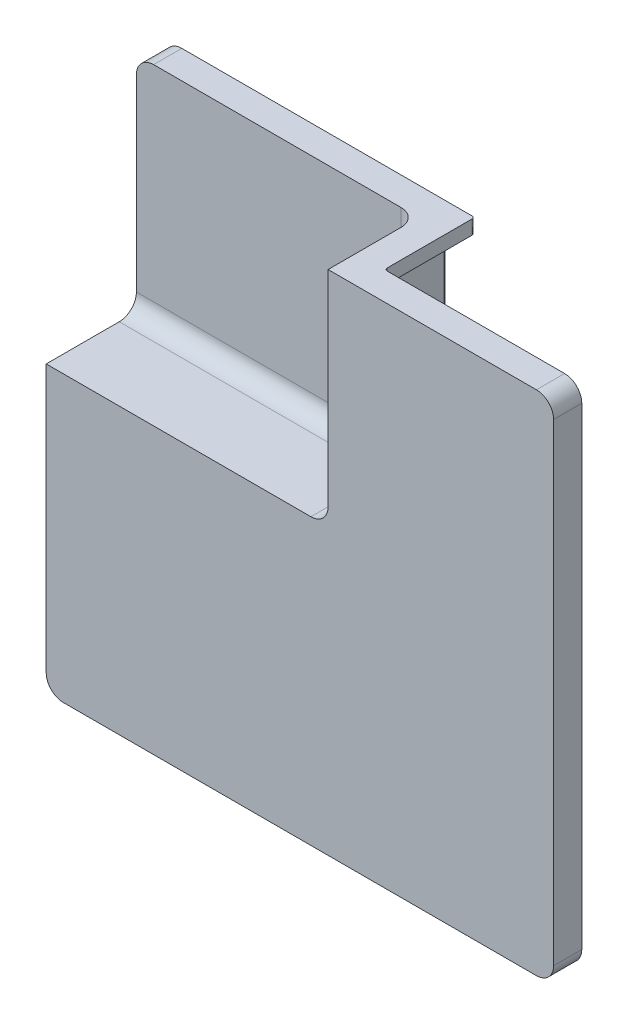
SolidWorks part; units mm, degrees
ref_plane "Front Plane" through (0, 0, 0) normal (0, 0, 1) x (1, 0, 0)
ref_plane "Top Plane" through (0, 0, 0) normal (0, 1, 0) x (1, 0, 0)
ref_plane "Right Plane" through (0, 0, 0) normal (1, 0, 0) x (0, 0, -1)
sketch "Sketch1" plane through (0, 0, 0) normal (0, 0, 1) x (1, 0, 0)
  line L1 (-57.2063, 108.3793) -> (110.5937, 108.3793)
  line L2 (-63.3063, 102.2793) -> (-63.3063, -65.5207)
  line L3 (-57.2063, -71.6207) -> (110.5937, -71.6207)
  line L4 (116.6937, 102.2793) -> (116.6937, -65.5207)
  arc A0 (-57.2063, 108.3793) -> (-63.3063, 102.2793) centre (-57.2063, 102.2793) ccw
  arc A1 (116.6937, 102.2793) -> (110.5937, 108.3793) centre (110.5937, 102.2793) ccw
  arc A2 (110.5937, -71.6207) -> (116.6937, -65.5207) centre (110.5937, -65.5207) ccw
  arc A3 (-63.3063, -65.5207) -> (-57.2063, -71.6207) centre (-57.2063, -65.5207) ccw
  dimension "D3" = 12.2
  dimension "D1" = 180
  dimension "D4" = 2
extrude "Boss-Extrude1" add sketch "Sketch1" along normal blind 5 contours A0 L2 L3 L4 L1 region at (26.6937, 18.3793, 0)
sketch "Sketch3" plane through (0, 0, 5) normal (0, 0, 1) x (1, 0, 0)
  line L0 (-63.3067, 18.3794) -> (116.6933, 18.3794) construction
  line L1 (26.6933, 108.3794) -> (26.6933, -71.6206) construction
  line L2 (-52.2067, -66.6206) -> (105.5933, -66.6206)
  line L3 (-58.3067, -60.5206) -> (-58.3067, 97.2794)
  line L4 (-52.2067, 103.3794) -> (105.5933, 103.3794)
  line L5 (111.6933, -60.5206) -> (111.6933, 97.2794)
  line L6 (-58.3067, -66.6206) -> (111.6933, 103.3794) construction
  line L7 (-58.3067, 103.3794) -> (111.6933, -66.6206) construction
  circle A0 centre (-52.2067, 97.2794) radius 6.1
  arc A1 (111.6933, 97.2794) -> (105.5933, 103.3794) centre (105.5933, 97.2794) ccw
  arc A2 (105.5933, -66.6206) -> (111.6933, -60.5206) centre (105.5933, -60.5206) ccw
  arc A3 (-58.3067, -60.5206) -> (-52.2067, -66.6206) centre (-52.2067, -60.5206) ccw
  point P4 (26.6933, 18.3794)
  line M1 (-63.3063, 102.2793) -> (-63.3063, -65.5207)
  arc M2 (-63.3063, -65.5207) -> (-57.2063, -71.6207) centre (-57.2063, -65.5207) ccw
  line M3 (-57.2063, -71.6207) -> (110.5937, -71.6207)
  arc M4 (110.5937, -71.6207) -> (116.6937, -65.5207) centre (110.5937, -65.5207) ccw
  line M5 (116.6937, -65.5207) -> (116.6937, 102.2793)
  arc M6 (116.6937, 102.2793) -> (110.5937, 108.3793) centre (110.5937, 102.2793) ccw
  line M7 (110.5937, 108.3793) -> (-57.2063, 108.3793)
  arc M8 (-57.2063, 108.3793) -> (-63.3063, 102.2793) centre (-57.2063, 102.2793) ccw
  dimension "D1" = 12.2
extrude "Boss-Extrude2" add sketch "Sketch3" against normal blind 10 contours A3 L3 A0 L4 A1 L5 A2 L2 M8 M1 M2 M3 M4 M5 M6 M7 region at (-59.7197, 104.7926, 5)
sketch "Sketch4" plane through (0, 0, 5) normal (0, 0, 1) x (1, 0, 0)
  line L0 (-63.3063, 102.2793) -> (-63.3063, -65.5207) construction
  line L1 (-63.3063, 29.3793) -> (36.6937, 29.3793)
  line L2 (-63.3063, 29.3793) -> (-63.3063, 108.3793)
  line L3 (-63.3063, 108.3793) -> (36.6937, 108.3793)
  line L4 (36.6937, 29.3793) -> (36.6937, 108.3793)
  line L5 (110.5937, 108.3793) -> (-57.2063, 108.3793) construction
  dimension "D1" = 100
  dimension "D2" = 79
extrude "Cut-Extrude1" cut sketch "Sketch4" against normal mid plane 60
sketch "Sketch5" plane through (0, 0, 5) normal (0, 0, 1) x (1, 0, 0)
  line L0 (36.6937, 29.3793) -> (36.6937, 108.3793) construction
  line L1 (36.6937, 108.3793) -> (41.6937, 108.3793)
  line L2 (36.6937, 108.3793) -> (36.6937, 35.4793)
  line L4 (41.6937, 108.3793) -> (41.6937, 30.4793)
  line L5 (30.5937, 29.3793) -> (-63.3063, 29.3793)
  line L8 (-63.3063, 29.3793) -> (-63.3063, 24.3793)
  line L12 (-63.3063, 29.3793) -> (-63.3063, -65.5207) construction
  line L13 (110.5937, 108.3793) -> (36.6937, 108.3793) construction
  line L15 (-57.2063, -71.6207) -> (110.5937, -71.6207) construction
  line L16 (35.5937, 24.3793) -> (-63.3063, 24.3793)
  arc A2 (30.5937, 29.3793) -> (36.6937, 35.4793) centre (30.5937, 35.4793) ccw
  arc A3 (35.5937, 24.3793) -> (41.6937, 30.4793) centre (35.5937, 30.4793) ccw
  point P3 (41.6937, 11.8614)
  point P13 (0, 0)
  point P22 (51.9986, 19.3793)
  dimension "D3" = 12.2
  dimension "D4" = 12.2
  dimension "D1" = 5
  dimension "D2" = 96
  dimension "D5" = 5
extrude "Boss-Extrude3" add sketch "Sketch5" against normal blind 37
sketch "Sketch8" plane through (36.6937, 0, 0) normal (-1, 0, 0) x (0, 0, 1)
  line L0 (-32, 29.3793) -> (5, 29.3793) construction
  line L1 (-32, 108.3793) -> (-27, 108.3793)
  line L2 (-32, 108.3793) -> (-32, 29.3793)
  line L3 (-32, 29.3793) -> (-27, 29.3793)
  line L4 (-27, 108.3793) -> (-27, 29.3793)
  dimension "D1" = 5
extrude "Boss-Extrude6" add sketch "Sketch8" along normal up to surface (100 mm away) up to face at (-63.3063, -3.9207, -10.6667)
fillet "Fillet3" radius 6.1 1 edges at (-63.3063, 108.3793, -29.5)
fillet "Fillet4" radius 6.1 3 edges at (-16.3563, 29.3793, -27) (34.907, 31.1659, -27) (36.6937, 71.9293, -27)
sketch "Sketch9" plane through (0, 0, -32) normal (0, 0, -1) x (-1, 0, 0)
  line L1 (-41.6937, 103.3793) -> (52.2063, 103.3793)
  line L2 (-41.6937, 103.3793) -> (-41.6937, 108.3793)
  line L3 (-41.6937, 108.3793) -> (57.2063, 108.3793)
  line L8 (63.3067, 24.3793) -> (58.3067, 24.3793)
  line L10 (-110.5937, 108.3793) -> (-41.6937, 108.3793) construction
  line L11 (63.3063, 102.2793) -> (53.5151, 102.2793) construction
  line L12 (57.2063, 108.3793) -> (57.2063, 102.2793) construction
  line L14 (63.3067, 24.3793) -> (63.3063, 102.2793)
  line L15 (58.3063, 97.2793) -> (58.3067, 24.3793)
  arc A0 (63.3063, 102.2793) -> (57.2063, 108.3793) centre (57.2063, 102.2793) ccw
  arc A1 (58.3063, 97.2793) -> (52.2063, 103.3793) centre (52.2063, 97.2793) ccw
  dimension "D2" = 12.2
  dimension "D3" = 6.1
  dimension "D1" = 5
  dimension "D4" = 5
extrude "Boss-Extrude7" add sketch "Sketch9" along normal blind 5
sketch "Sketch10" plane through (0, 24.3793, 0) normal (0, -1, 0) x (1, 0, 0)
  line L0 (-63.3063, -5) -> (-58.3067, -5) construction
  line L1 (-63.3067, -37) -> (-58.3067, -37)
  line L2 (-63.3067, -37) -> (-63.3067, -5)
  line L3 (-63.3067, -5) -> (-58.3067, -5)
  line L4 (-58.3067, -37) -> (-58.3067, -5)
  line L5 (-63.3063, -5) -> (-57.2063, -5) construction
extrude "Boss-Extrude8" add sketch "Sketch10" along normal blind 5
sketch "Sketch11" plane through (41.6937, 0, 0) normal (1, 0, 0) x (0, 0, -1)
  line L1 (37, 108.3793) -> (5, 108.3793)
  line L2 (37, 108.3793) -> (37, 103.3793)
  line L3 (37, 103.3793) -> (5, 103.3793)
  line L4 (5, 108.3793) -> (5, 103.3793)
  dimension "D1" = 5
extrude "Boss-Extrude9" add sketch "Sketch11" along normal blind 5
fillet "Fillet6" radius 1 17 edges at (73.6435, 103.3794, 0) (109.9067, 101.5927, 0) (111.6933, 18.3794, 0) (109.9067, -64.834, 0) (26.6933, -66.6206, 0) (-56.52, -64.834, 0) (41.6937, 66.9293, 0) (39.907, 26.1659, 0) (41.6937, 66.9293, -32) (39.907, 26.1659, -32) (-58.3067, -18.0707, 0) (-60.8067, 19.3793, -37) (-60.8065, 19.3793, -5) (46.6937, 105.8793, -5) (46.6937, 105.8793, -37) (-11.3565, 24.3793, 0)
